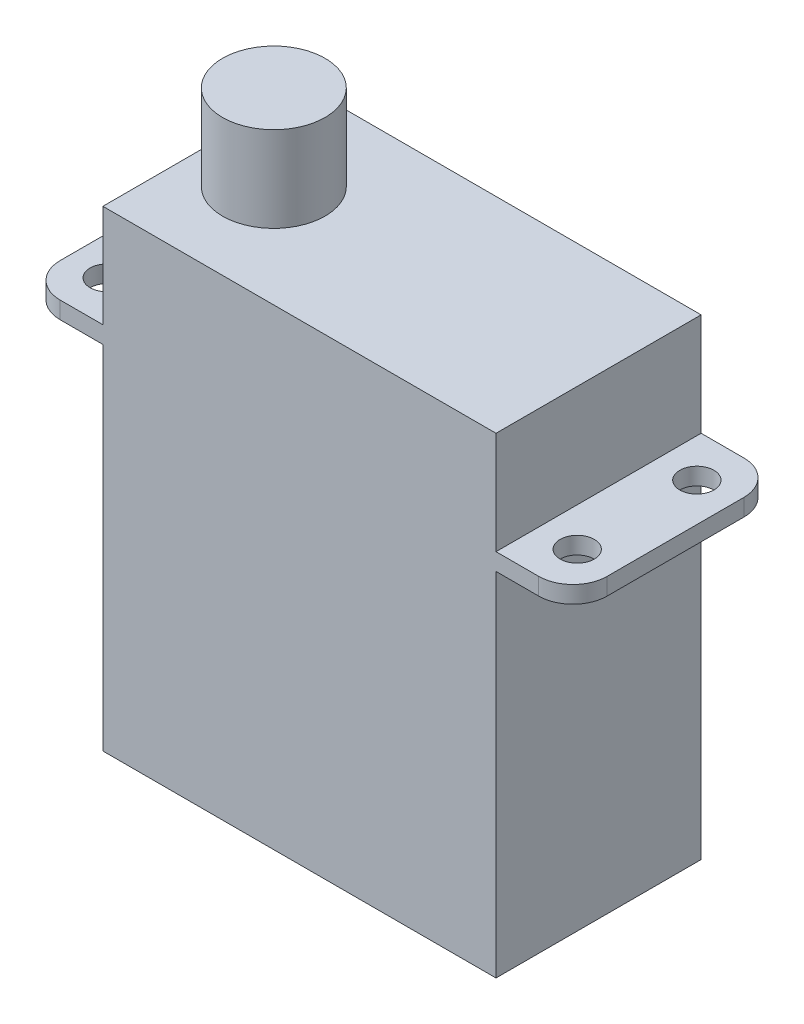
SolidWorks part; units mm, degrees
ref_plane "Front Plane" through (0, 0, 0) normal (0, 0, 1) x (1, 0, 0)
ref_plane "Top Plane" through (0, 0, 0) normal (0, 1, 0) x (1, 0, 0)
ref_plane "Right Plane" through (0, 0, 0) normal (1, 0, 0) x (0, 0, -1)
sketch "Эскиз1" plane through (0, 0, 0) normal (0, 0, 1) x (1, 0, 0)
  line L0 (0, 5.0732) -> (0, -2.902) construction
  line L1 (-11.5, -13.8) -> (11.5, -13.8)
  line L2 (-11.5, -13.8) -> (-11.5, 13.8)
  line L3 (-11.5, 13.8) -> (11.5, 13.8)
  line L4 (11.5, -13.8) -> (11.5, 13.8)
  line L5 (-11.5, -13.8) -> (11.5, 13.8) construction
  line L6 (-11.5, 13.8) -> (11.5, -13.8) construction
  line L7 (-16, 6.8) -> (-11.5, 6.8)
  line L8 (-16, 6.8) -> (-16, 7.8)
  line L9 (-16, 7.8) -> (-11.5, 7.8)
  line L10 (-11.5, 6.8) -> (-11.5, 7.8)
  line L11 (-16, 6.8) -> (-11.5, 7.8) construction
  line L12 (-16, 7.8) -> (-11.5, 6.8) construction
  line L13 (16, 7.8) -> (11.5, 7.8)
  line L14 (11.5, 6.8) -> (11.5, 7.8)
  line L15 (16, 6.8) -> (11.5, 6.8)
  line L16 (16, 6.8) -> (16, 7.8)
  point P0 (0, 0)
  point P5 (-13.75, 7.3)
  dimension "D1" = 23
  dimension "D2" = 27.6
  dimension "D3" = 20.6
  dimension "D4" = 1
  dimension "D5" = 32
extrude "Бобышка-Вытянуть1" add sketch "Эскиз1" along normal mid plane 12 contours L1 L4 L3 L2 | L9 L8 L7 L2 | L15 L16 L13 L4 region at (0, 0, 0) region at (-13.75, 7.3, 0) region at (13.75, 7.3, 0)
sketch "Эскиз2" plane through (0, 13.8, 0) normal (0, 1, 0) x (1, 0, 0)
  line L0 (-11.5, 0) -> (11.5, 0) construction
  line L1 (-11.5, -6) -> (-11.5, 6) construction
  line L2 (11.5, -6) -> (11.5, 6) construction
  circle A0 centre (-7.5, 0) radius 3
  dimension "D1" = 6
  dimension "D2" = 4
extrude "Бобышка-Вытянуть2" add sketch "Эскиз2" along normal blind 5
sketch "Эскиз3" plane through (0, 7.8, 0) normal (0, 1, 0) x (1, 0, 0)
  line L0 (-13.75, 6) -> (-13.75, -6) construction
  line L1 (-16, 6) -> (-11.5, 6) construction
  line L2 (-16, -6) -> (-11.5, -6) construction
  line L3 (0, -6) -> (0, 6) construction
  line L4 (-11.5, -6) -> (11.5, -6) construction
  line L5 (-11.5, 6) -> (11.5, 6) construction
  circle A0 centre (-13.75, 3.5) radius 1
  circle A1 centre (-13.75, -3.5) radius 1
  circle A2 centre (13.75, -3.5) radius 1
  circle A3 centre (13.75, 3.5) radius 1
  dimension "D1" = 2
  dimension "D2" = 7
  dimension "D3" = 2.5
extrude "Вырез-Вытянуть1" cut sketch "Эскиз3" against normal through all both and the other way through all
fillet "Скругление1" radius 2 4 edges at (-16, 7.3, -6) (16, 7.3, -6) (16, 7.3, 6) (-16, 7.3, 6)
